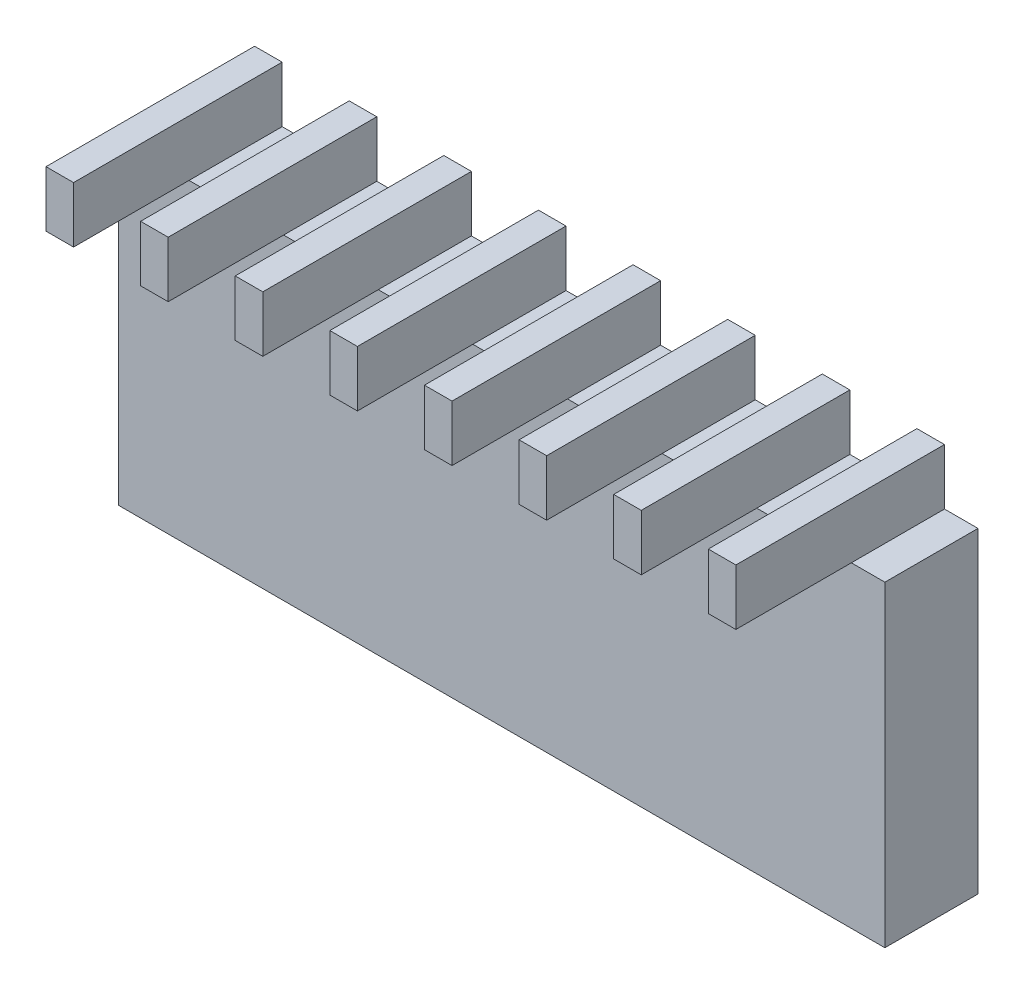
SolidWorks part; units mm, degrees
ref_plane "前视基准面" through (0, 0, 0) normal (0, 0, 1) x (1, 0, 0)
ref_plane "上视基准面" through (0, 0, 0) normal (0, 1, 0) x (1, 0, 0)
ref_plane "右视基准面" through (0, 0, 0) normal (1, 0, 0) x (0, 0, -1)
other "Configuration Table"
sketch "草图1" plane through (0, 0, 0) normal (0, 0, 1) x (1, 0, 0)
  line L0 (7.3822, -4.2023) -> (7.3822, 4.2977) construction
  line L1 (-5.5678, 4.2977) -> (20.3322, 4.2977)
  line L2 (-5.5678, 4.2977) -> (-5.5678, -4.2023)
  line L3 (-5.5678, -4.2023) -> (20.3322, -4.2023)
  line L4 (20.3322, 4.2977) -> (20.3322, -4.2023)
  line L5 (-4.4178, 5.7977) -> (19.1822, 5.7977)
  line L6 (-4.4178, 5.7977) -> (-4.4178, 4.2977)
  line L7 (-4.4178, 4.2977) -> (19.1822, 4.2977)
  line L8 (19.1822, 5.7977) -> (19.1822, 4.2977)
  dimension "D1" = 8.5
  dimension "D2" = 25.9
  dimension "D3" = 23.6
  dimension "D4" = 10
  dimension "D5" = 1.15
extrude "凸台-拉伸1" add sketch "草图1" along normal blind 2.5 contours L3 L4 L1 L2
extrude "凸台-拉伸2" add sketch "草图1<5>" along normal blind 2.5 contours L5 L8 L7 L6
sketch "草图1<5>" plane through (0, 0, 0) normal (0, 0, 1) x (1, 0, 0) same geometry as "草图1"
sketch "草图2" plane through (0, 0, 2.5) normal (0, 0, 1) x (1, 0, 0)
  line L0 (-4.4178, 4.2977) -> (19.1822, 4.2977)
  line L1 (-4.4178, 5.7977) -> (-4.4178, 4.2977) construction
  line L2 (-4.4178, 5.7977) -> (19.1822, 5.7977) construction
  line L3 (19.1822, 5.7977) -> (19.1822, 4.2977) construction
  line L4 (19.1822, 5.7977) -> (19.1822, 4.2977)
  line L5 (-4.4178, 5.7977) -> (19.1822, 5.7977)
  line L6 (-4.4178, 5.7977) -> (-4.4178, 4.2977)
extrude "凸台-拉伸3" add sketch "草图2" along normal blind 3.1
sketch "草图3" plane through (0, 5.7977, 0) normal (0, 1, 0) x (1, 0, 0)
  line L0 (19.1822, -5.6) -> (-4.4178, -5.6) construction
  line L1 (16.6422, 0) -> (18.4422, 0)
  line L2 (16.6422, 0) -> (16.6422, -5.6)
  line L3 (16.6422, -5.6) -> (18.4422, -5.6)
  line L4 (18.4422, 0) -> (18.4422, -5.6)
  line L5 (19.1822, -5.6) -> (19.1822, 0) construction
  line L6 (14.1022, 0) -> (14.1022, -5.6)
  line L7 (14.1022, 0) -> (15.9022, 0)
  line L8 (15.9022, 0) -> (15.9022, -5.6)
  line L9 (14.1022, -5.6) -> (15.9022, -5.6)
  line L10 (11.5622, 0) -> (11.5622, -5.6)
  line L11 (11.5622, 0) -> (13.3622, 0)
  line L12 (13.3622, 0) -> (13.3622, -5.6)
  line L13 (11.5622, -5.6) -> (13.3622, -5.6)
  line L14 (9.0222, 0) -> (9.0222, -5.6)
  line L15 (9.0222, 0) -> (10.8222, 0)
  line L16 (10.8222, 0) -> (10.8222, -5.6)
  line L17 (9.0222, -5.6) -> (10.8222, -5.6)
  line L18 (6.4822, 0) -> (6.4822, -5.6)
  line L19 (6.4822, 0) -> (8.2822, 0)
  line L20 (8.2822, 0) -> (8.2822, -5.6)
  line L21 (6.4822, -5.6) -> (8.2822, -5.6)
  line L22 (3.9422, 0) -> (3.9422, -5.6)
  line L23 (3.9422, 0) -> (5.7422, 0)
  line L24 (5.7422, 0) -> (5.7422, -5.6)
  line L25 (3.9422, -5.6) -> (5.7422, -5.6)
  line L26 (1.4022, 0) -> (1.4022, -5.6)
  line L27 (1.4022, 0) -> (3.2022, 0)
  line L28 (3.2022, 0) -> (3.2022, -5.6)
  line L29 (1.4022, -5.6) -> (3.2022, -5.6)
  line L30 (-1.1378, 0) -> (-1.1378, -5.6)
  line L31 (-1.1378, 0) -> (0.6622, 0)
  line L32 (0.6622, 0) -> (0.6622, -5.6)
  line L33 (-1.1378, -5.6) -> (0.6622, -5.6)
  line L34 (-3.6778, 0) -> (-3.6778, -5.6)
  line L35 (-3.6778, 0) -> (-1.8778, 0)
  line L36 (-1.8778, 0) -> (-1.8778, -5.6)
  line L37 (-3.6778, -5.6) -> (-1.8778, -5.6)
  dimension "D1" = 1.8
  dimension "D2" = 0.74
  dimension "D3" = 9
extrude "切除-拉伸1" cut sketch "草图3" against normal blind 1.5
sketch "草图4" plane through (0, 4.2977, 0) normal (0, 1, 0) x (1, 0, 0)
  line L1 (15.0022, 1.4866) -> (23.7721, 1.4866)
  line L2 (15.0022, 1.4866) -> (15.0022, -6.2433)
  line L3 (15.0022, -6.2433) -> (23.7721, -6.2433)
  line L4 (23.7721, 1.4866) -> (23.7721, -6.2433)
  line L5 (15.9022, -5.6) -> (15.9022, 0) construction
  dimension "D1" = 0.9
extrude "切除-拉伸2" cut sketch "草图4" against normal blind 10 and the other way blind 2
